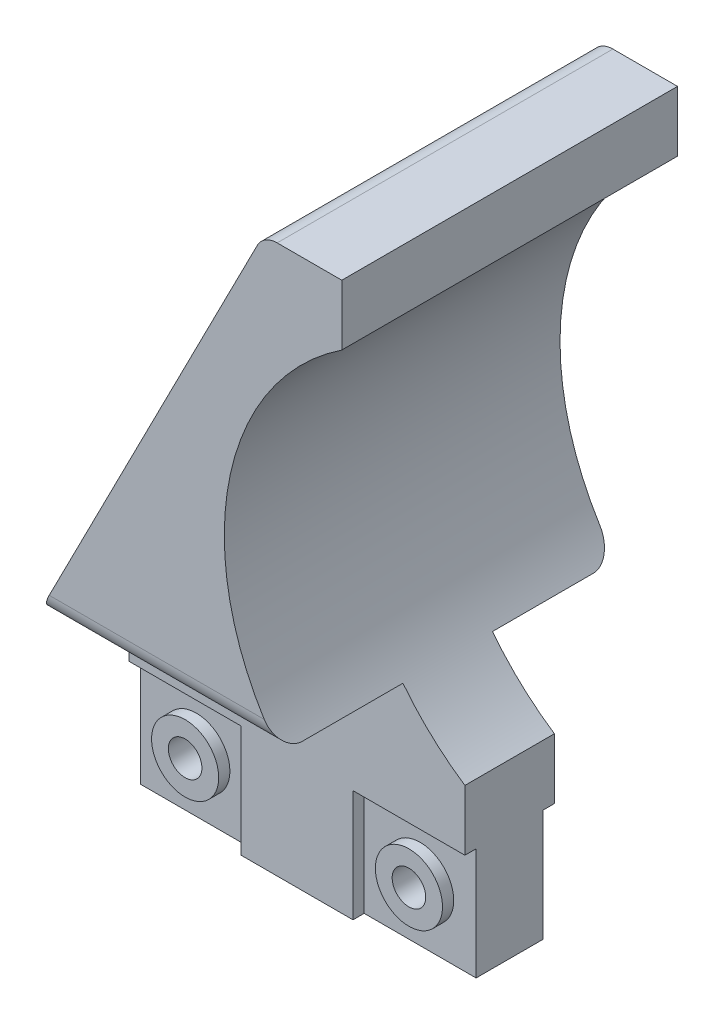
SolidWorks part; units mm, degrees
ref_plane "前视基准面" through (0, 0, 0) normal (0, 0, 1) x (1, 0, 0)
ref_plane "上视基准面" through (0, 0, 0) normal (0, 1, 0) x (1, 0, 0)
ref_plane "右视基准面" through (0, 0, 0) normal (1, 0, 0) x (0, 0, -1)
sketch "草图1" plane through (0, 0, 0) normal (0, 0, 1) x (1, 0, 0)
  line L0 (0, 63.1639) -> (0, -26.3861) construction
  line L1 (-25.198, 0) -> (25, 0) construction
  line L2 (-15, 0) -> (15, 0)
  line L5 (-24.3527, 35) -> (25, 35) construction
  line L6 (-23.2185, 5) -> (17.875, 5) construction
  line L7 (-15, 0) -> (-15, 15)
  line L8 (-15, 15) -> (8, 60)
  line L9 (8, 60) -> (15, 60)
  line L10 (15, 60) -> (15, 54.5959)
  line L11 (15, 15.4041) -> (15, 0)
  circle A1 centre (-10, 5) radius 1.5
  circle A2 centre (10, 5) radius 1.5
  arc A3 (15, 54.5959) -> (15, 15.4041) centre (28.0357, 35) ccw
  dimension "D13" = 3
  dimension "D14" = 3
  dimension "D1" = 15
  dimension "D2" = 15
  dimension "D3" = 35
  dimension "D4" = 15
  dimension "D6" = 15
  dimension "D7" = 60
  dimension "D8" = 25
  dimension "D9" = 7
  dimension "D10" = 5
  dimension "D11" = 10
  dimension "D12" = 10
extrude "凸台-拉伸1" add sketch "草图1" along normal blind 8
sketch "草图2" plane through (0, 0, 0) normal (0, 0, 1) x (1, 0, 0)
  line L1 (8, 60) -> (-15, 15) construction
  line L2 (-12.1664, 20.544) -> (8, 60)
  line L3 (8, 60) -> (15, 60)
  line L4 (15, 60) -> (15, 54.5959)
  line L5 (-12.1664, 20.544) -> (9.4628, 20.544)
  arc A0 (15, 54.5959) -> (15, 15.4041) centre (28.0357, 35) ccw construction
  arc A3 (15, 54.5959) -> (9.4628, 20.544) centre (28.0357, 35) ccw
extrude "凸台-拉伸2" add sketch "草图2" along normal blind 19 and the other way blind 11
fillet "圆角1" radius 2 1 edges at (-1.3518, 20.544, 19)
fillet "圆角2" radius 2 1 edges at (-1.3518, 20.544, -11)
fillet "圆角4" radius 2 1 edges at (8, 60, 4)
fillet "圆角5" radius 2 2 edges at (15, 0, 4) (-15, 0, 4)
sketch "草图3" plane through (0, 0, 0) normal (0, 0, -1) x (-1, 0, 0)
  line L0 (-15, 2) -> (-15, 15.4041) construction
  line L1 (-15, 10) -> (-5, 10)
  line L2 (-15, 10) -> (-15, 0)
  line L3 (-15, 0) -> (-5, 0)
  line L4 (-5, 10) -> (-5, 0)
  line L5 (13, 0) -> (-13, 0) construction
  line L6 (15, 15) -> (15, 2) construction
  line L7 (15, 10) -> (5, 10)
  line L8 (15, 10) -> (15, 0)
  line L9 (15, 0) -> (5, 0)
  line L10 (5, 10) -> (5, 0)
  circle A0 centre (-10, 5) radius 3
  circle A1 centre (10, 5) radius 3
  dimension "D1" = 10
  dimension "D2" = 10
  dimension "D3" = 10
  dimension "D4" = 10
extrude "切除-拉伸1" cut sketch "草图3" against normal blind 8
extrude "凸台-拉伸3" add sketch "草图3<2>" against normal blind 7
sketch "草图3<2>" plane through (0, 0, 0) normal (0, 0, -1) x (-1, 0, 0) same geometry as "草图3"
extrude "切除-拉伸2" cut sketch "草图3<3>" against normal blind 1
sketch "草图3<3>" plane through (0, 0, 0) normal (0, 0, -1) x (-1, 0, 0) same geometry as "草图3"
